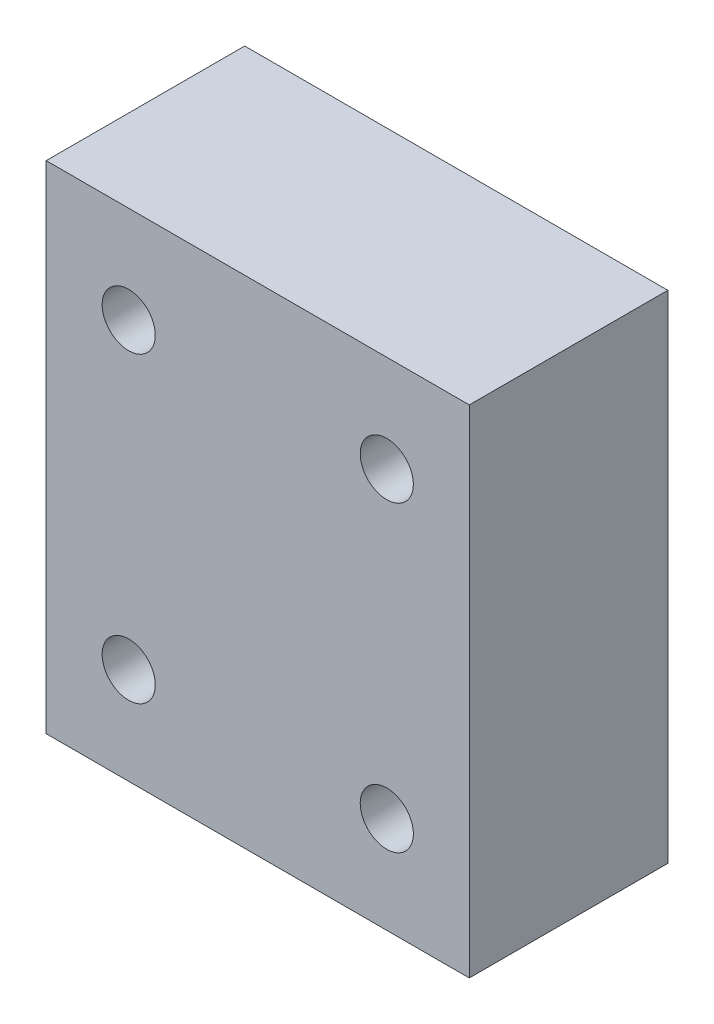
SolidWorks part; units mm, degrees
ref_plane "Front Plane" through (0, 0, 0) normal (0, 0, 1) x (1, 0, 0)
ref_plane "Top Plane" through (0, 0, 0) normal (0, 1, 0) x (1, 0, 0)
ref_plane "Right Plane" through (0, 0, 0) normal (1, 0, 0) x (0, 0, -1)
sketch "Sketch1" plane through (0, 0, 0) normal (0, 0, 1) x (1, 0, 0)
  line L0 (0, 25) -> (0, -25) construction
  line L1 (21.3115, 25) -> (-21.3115, 25)
  line L2 (21.3115, 25) -> (21.3115, -25)
  line L3 (21.3115, -25) -> (-21.3115, -25)
  line L4 (-21.3115, 25) -> (-21.3115, -25)
  line L5 (21.3115, 25) -> (-21.3115, -25) construction
  line L6 (21.3115, -25) -> (-21.3115, 25) construction
  line L7 (-21.3115, 0) -> (21.3115, 0) construction
  circle A0 centre (-13, -15.25) radius 2.677
  circle A1 centre (13, -15.25) radius 2.677
  circle A2 centre (13, 15.25) radius 2.677
  circle A3 centre (-13, 15.25) radius 2.677
  point P0 (0, 0)
  dimension "D1" = 30.5
  dimension "D2" = 26
  dimension "D3" = 50
extrude "Boss-Extrude1" add sketch "Sketch1" along normal blind 20
sketch "Sketch2" plane through (0, 0, 0) normal (0, 0, 1) x (1, 0, 0)
  circle A0 centre (0, 0) radius 8.73
  dimension "D1" = 17.46
extrude "Cut-Extrude2" cut sketch "Sketch2" along normal blind 7.94
